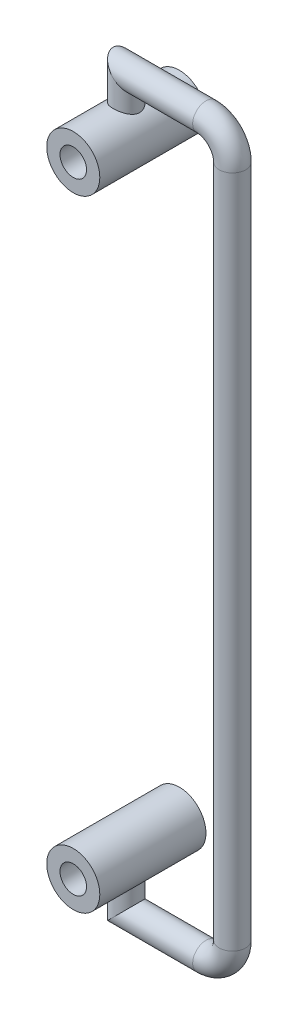
SolidWorks part; units mm, degrees
ref_plane "Plan de face" through (0, 0, 0) normal (0, 0, 1) x (1, 0, 0)
ref_plane "Plan de dessus" through (0, 0, 0) normal (0, 1, 0) x (1, 0, 0)
ref_plane "Plan de droite" through (0, 0, 0) normal (1, 0, 0) x (0, 0, -1)
sketch "Esquisse1" plane through (0, 0, 0) normal (0, 0, 1) x (1, 0, 0)
  line L0 (0, 0) -> (15, 0)
  line L1 (20, 5) -> (20, 132)
  line L2 (15, 137) -> (0, 137)
  line L3 (0, 137) -> (0, 127)
  line L4 (0, 0) -> (0, 10)
  arc A0 (15, 0) -> (20, 5) centre (15, 5) ccw
  arc A1 (20, 132) -> (15, 137) centre (15, 132) ccw
  point P9 (20, 0)
  dimension "D5" = 5
  dimension "D1" = 117
  dimension "D2" = 10
  dimension "D3" = 10
  dimension "D4" = 20
ref_plane "Plan1" through (0, 127, 0) normal (0, 1, 0) x (1, 0, 0)
sketch "Esquisse2" plane through (0, 127, 0) normal (0, 1, 0) x (1, 0, 0)
  circle A0 centre (0, 0) radius 2.5
  dimension "D1" = 5
sweep "Balayage1" add profiles "Esquisse2" path "Esquisse1"
sketch "Esquisse3" plane through (0, 0, 0) normal (0, 0, 1) x (1, 0, 0)
  line L0 (-2.5, 127) -> (2.5, 127) construction
  line L1 (2.5, 10) -> (-2.5, 10) construction
  circle A0 centre (0, 127) radius 5
  circle A1 centre (0, 10) radius 5
  circle A2 centre (0, 127) radius 2.5
  circle A3 centre (0, 10) radius 2.5
  dimension "D1" = 10
  dimension "D2" = 10
  dimension "D3" = 5
  dimension "D4" = 5
extrude "Boss.-Extru.1" add sketch "Esquisse3" along normal blind 10 and the other way blind 10
sketch "Esquisse5" plane through (0, 0, 10) normal (0, 0, 1) x (1, 0, 0)
  line L0 (2.5, 10) -> (-2.5, 10) construction
  circle A0 centre (0, 127) radius 2.5
  circle A1 centre (0, 10) radius 2.5
extrude "Enlèv. mat.-Extru.1" cut sketch "Esquisse5" against normal through all
